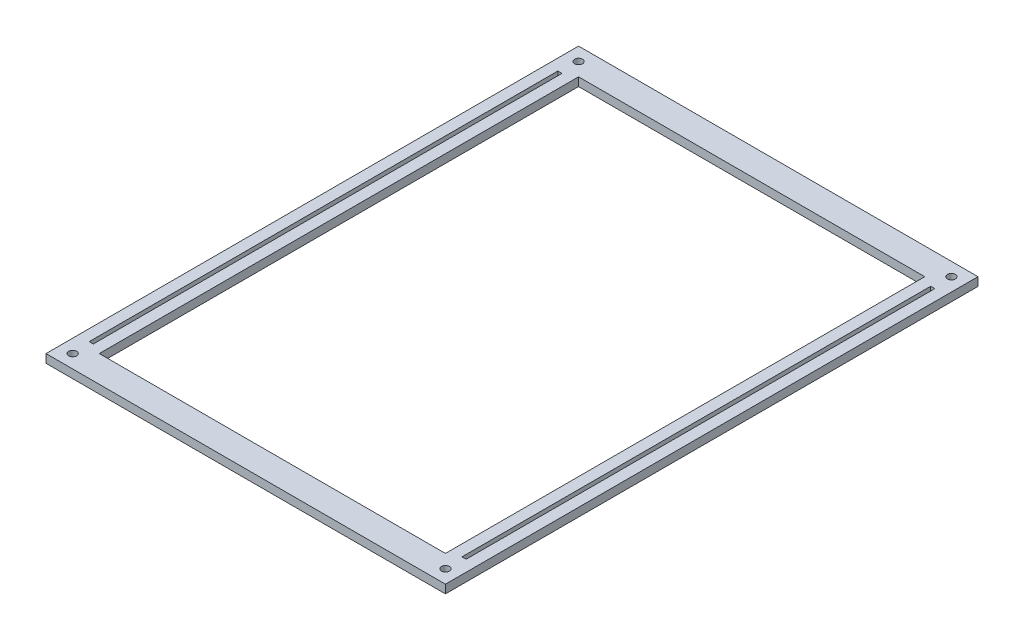
SolidWorks part; units mm, degrees
ref_plane "Front Plane" through (0, 0, 0) normal (0, 0, 1) x (1, 0, 0)
ref_plane "Top Plane" through (0, 0, 0) normal (0, 1, 0) x (1, 0, 0)
ref_plane "Right Plane" through (0, 0, 0) normal (1, 0, 0) x (0, 0, -1)
sketch "Sketch1" plane through (0, 0, 0) normal (0, 1, 0) x (1, 0, 0)
  line L0 (-65, 90) -> (65, 90)
  line L5 (-75, -100) -> (75, -100)
  line L6 (-75, -100) -> (-75, 100)
  line L7 (-75, 100) -> (75, 100)
  line L8 (75, -100) -> (75, 100)
  line L9 (-75, -100) -> (75, 100) construction
  line L10 (-75, 100) -> (75, -100) construction
  line L11 (65, -90) -> (65, 90)
  line L12 (-65, -90) -> (65, -90)
  line L13 (-65, -90) -> (-65, 90)
  line L32 (0, 100) -> (0, -100) construction
  point P0 (0, 0)
  dimension "D2" = 150
  dimension "D3" = 200
  dimension "D1" = 10
extrude "MainBody" add sketch "Sketch1" along normal mid plane 3.175
sketch "Sketch2" plane through (0, 1.5875, 0) normal (0, 1, 0) x (1, 0, 0)
  line L0 (-65, 88) -> (-75, 88) construction
  line L4 (-65, 90) -> (-65, -90) construction
  line L10 (-75, 100) -> (-75, -100) construction
  line L11 (-70, 88) -> (-70, 0) construction
  line L12 (65, 90) -> (-65, 90) construction
  line L13 (75, 100) -> (-75, 100) construction
  line L18 (0, 0) -> (0, 100) construction
  line L27 (-70.7779, -88) -> (-69.2221, -88)
  line L28 (-70.7779, -88) -> (-70.7779, 88)
  line L29 (-70.7779, 88) -> (-69.2221, 88)
  line L30 (-69.2221, -88) -> (-69.2221, 88)
  line L31 (-70.7779, -88) -> (-69.2221, 88) construction
  line L32 (-70.7779, 88) -> (-69.2221, -88) construction
  dimension "D1" = 2
  dimension "D2" = 1.5557
extrude "SheetLock" cut sketch "Sketch2" against normal up to next
mirror "Mirror1" about plane through (0, 0, 0) normal (1, 0, 0) of "SheetLock"
sketch "Sketch3" plane through (0, 1.5875, 0) normal (0, 1, 0) x (1, 0, 0)
  line L0 (0, 100) -> (0, -100) construction
  line L1 (75, 100) -> (-75, 100) construction
  line L2 (-75, -100) -> (75, -100) construction
  line L3 (-75, 0) -> (75, 0) construction
  line L4 (-75, 100) -> (-75, -100) construction
  line L5 (75, -100) -> (75, 100) construction
  line L6 (-65, 90) -> (-65, 100) construction
  line L7 (-65, 90) -> (-75, 90) construction
  circle A0 centre (-70, 95) radius 1.5
  circle A1 centre (70, 95) radius 1.5
  circle A2 centre (70, -95) radius 1.5
  circle A3 centre (-70, -95) radius 1.5
  point P19 (-65, 95)
  point P20 (-70, 90)
  dimension "D1" = 3
extrude "SupportHoles" cut sketch "Sketch3" against normal up to next
equation "\"SheetLockLengthOffset\"=2"
equation "\"SheetThickness\"=0.79375"
equation "\"SheetThicknessTolerance\"= 0.015in"
equation "\"LowerBasketWidth\"=150"
equation "\"D2@Sketch1\"=\"LowerBasketWidth\""
equation "\"LowerBasketLength\"=200"
equation "\"D3@Sketch1\"=\"LowerBasketLength\""
equation "\"SupportHoleDiameter\"=3"
equation "\"D1@Sketch3\"=\"SupportHoleDiameter\""
equation "\"InnerGapOffset\"=10"
equation "\"D1@Sketch1\"=\"InnerGapOffset\""
equation "\"D1@Sketch2\"=\"SheetLockLengthOffset\""
equation "\"D2@Sketch2\"=\"SheetThickness\" + \"SheetThicknessTolerance\"*2"
